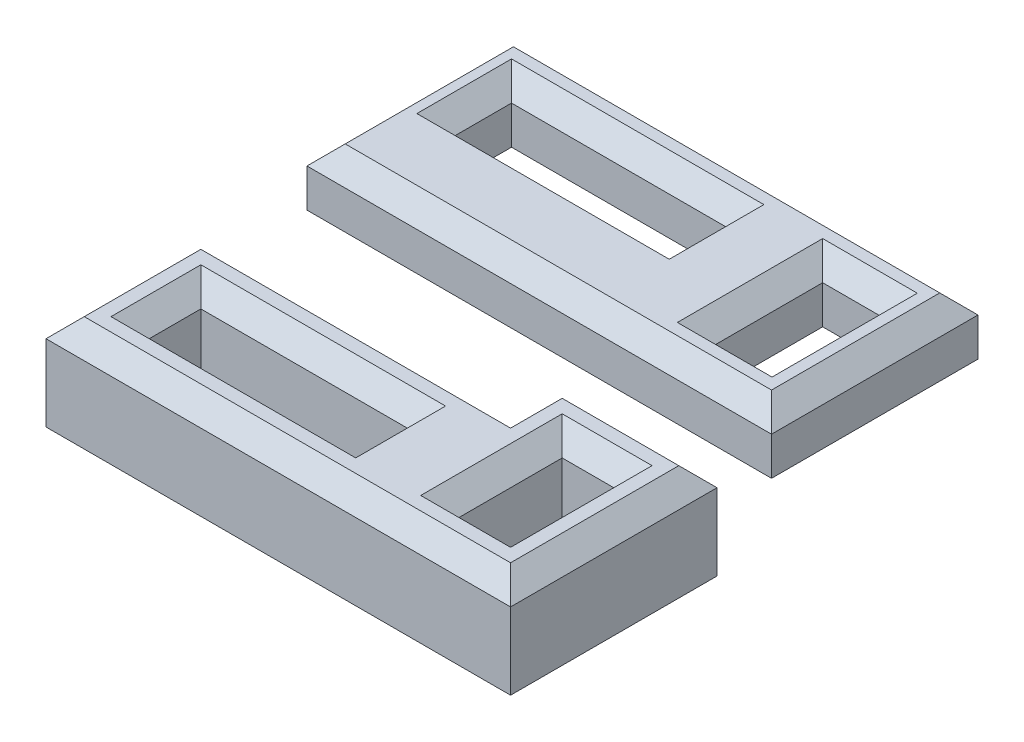
SolidWorks part; units mm, degrees
ref_plane "Front Plane" through (0, 0, 0) normal (0, 0, 1) x (1, 0, 0)
ref_plane "Top Plane" through (0, 0, 0) normal (0, 1, 0) x (1, 0, 0)
ref_plane "Right Plane" through (0, 0, 0) normal (1, 0, 0) x (0, 0, -1)
sketch "Sketch1" plane through (0, 0, 0) normal (0, 1, 0) x (1, 0, 0)
  line L12 (-12.15, -5.4) -> (12.15, -5.4)
  line L23 (4.05, 2.7) -> (6.75, 2.7) construction
  line L24 (-9.45, 0) -> (-9.45, 2.7) construction
  line L25 (12.15, 2.7) -> (9.45, 2.7) construction
  line L26 (-12.15, -2.7) -> (-9.45, -2.7) construction
  line L27 (9.45, 2.7) -> (9.45, 5.4) construction
  line L28 (-9.45, -2.7) -> (-9.45, -5.4) construction
  line L29 (4.05, -2.7) -> (6.75, -2.7) construction
  line L30 (1.35, -2.7) -> (4.05, -2.7) construction
  line L31 (-9.45, -2.7) -> (9.45, 2.7) construction
  line L32 (4.05, 2.7) -> (4.05, 5.4)
  line L33 (-12.15, 2.7) -> (4.05, 2.7)
  line L34 (12.15, -5.4) -> (12.15, 5.4)
  line L35 (4.05, 5.4) -> (12.15, 5.4)
  line L36 (-12.15, -5.4) -> (-12.15, 2.7)
  line L37 (9.45, -2.7) -> (9.45, 2.7)
  line L38 (6.75, 2.7) -> (9.45, 2.7)
  line L39 (6.75, -2.7) -> (6.75, 2.7)
  line L40 (6.75, -2.7) -> (9.45, -2.7)
  line L41 (1.35, -2.7) -> (1.35, 0)
  line L42 (-9.45, 0) -> (1.35, 0)
  line L43 (-9.45, -2.7) -> (-9.45, 0)
  line L44 (-9.45, -2.7) -> (1.35, -2.7)
  point P0 (-4.7205, 3.7182)
  dimension "D1" = 8.1
  dimension "D2" = 24.3
  dimension "D3" = 2.7
extrude "Boss-Extrude1" add sketch "Sketch1" along normal blind 2 and the other way blind 2
sketch "Sketch2" plane through (0, -2, 0) normal (0, -1, 0) x (1, 0, 0)
  line L0 (6.75, 2.7) -> (9.45, 2.7) construction
  line L1 (9.45, -2.7) -> (6.75, -2.7) construction
  line L4 (1.35, 2.7) -> (1.35, 0) construction
  line L5 (-9.45, 0) -> (-9.45, 2.7) construction
  line L6 (0.5, 1.35) -> (1.35, 1.35) construction
  line L7 (-8.6, 1.85) -> (-7.6, 1.85)
  line L8 (-8.6, 1.85) -> (-8.6, 0.85)
  line L9 (-8.6, 0.85) -> (-7.6, 0.85)
  line L10 (-7.6, 1.85) -> (-7.6, 0.85)
  line L11 (-5.9, 1.85) -> (-4.9, 1.85)
  line L12 (-5.9, 1.85) -> (-5.9, 0.85)
  line L13 (-5.9, 0.85) -> (-4.9, 0.85)
  line L14 (-4.9, 1.85) -> (-4.9, 0.85)
  line L15 (-3.2, 1.85) -> (-2.2, 1.85)
  line L16 (-3.2, 1.85) -> (-3.2, 0.85)
  line L17 (-3.2, 0.85) -> (-2.2, 0.85)
  line L18 (-2.2, 1.85) -> (-2.2, 0.85)
  line L19 (-0.5, 1.85) -> (0.5, 1.85)
  line L20 (-0.5, 1.85) -> (-0.5, 0.85)
  line L21 (-0.5, 0.85) -> (0.5, 0.85)
  line L22 (0.5, 1.85) -> (0.5, 0.85)
  line L23 (7.6, 1.85) -> (8.6, 1.85)
  line L24 (7.6, 1.85) -> (7.6, 0.85)
  line L25 (7.6, 0.85) -> (8.6, 0.85)
  line L26 (8.6, 1.85) -> (8.6, 0.85)
  line L27 (7.6, -0.85) -> (8.6, -0.85)
  line L28 (7.6, -0.85) -> (7.6, -1.85)
  line L29 (7.6, -1.85) -> (8.6, -1.85)
  line L30 (8.6, -0.85) -> (8.6, -1.85)
  line L31 (8.1, -2.7) -> (8.1, -1.85) construction
  line L32 (-12.15, 5.4) -> (12.15, 5.4)
  line L33 (12.15, 5.4) -> (12.15, -5.4)
  line L34 (-7.6, 1.35) -> (-6.75, 1.35) construction
  line L35 (-6.75, 1.35) -> (-5.9, 1.35) construction
  line L36 (8.1, -0.85) -> (8.1, 0) construction
  line L37 (-4.9, 1.35) -> (-4.05, 1.35) construction
  line L38 (-4.05, 1.35) -> (-3.2, 1.35) construction
  line L39 (8.1, 1.85) -> (8.1, 2.7) construction
  line L40 (-8.6, 1.35) -> (-9.45, 1.35) construction
  line L41 (12.15, -5.4) -> (4.05, -5.4)
  line L42 (4.05, -5.4) -> (4.05, -2.7) construction
  line L43 (8.1, 0) -> (8.1, 0.85) construction
  line L44 (12.15, -5.4) -> (4.05, -5.4) construction
  line L45 (-2.2, 1.35) -> (-1.35, 1.35) construction
  line L46 (-1.35, 1.35) -> (-0.5, 1.35) construction
  line L47 (4.05, -5.4) -> (4.05, -2.7)
  line L48 (4.05, -2.7) -> (-12.15, -2.7)
  line L49 (-12.15, -2.7) -> (-12.15, 5.4)
  point P6 (1.35, 1.35)
  dimension "D1" = 1
extrude "Boss-Extrude2" add sketch "Sketch2" along normal blind 1
chamfer "Chamfer3" distance 1 angle 45 14 edges at (0, 2, 5.4) (-4.05, 2, 2.7) (1.35, 2, 1.35) (-4.05, 2, 0) (-9.45, 2, 1.35) (-4.05, 2, -2.7) (4.05, 2, -4.05) (8.1, 2, -5.4) (12.15, 2, 0) (-12.15, 2, 1.35) (8.1, 2, 2.7) (9.45, 2, 0) (8.1, 2, -2.7) (6.75, 2, 0)
sketch "Sketch3" plane through (0, 0, 0) normal (0, 1, 0) x (1, 0, 0)
  line L1 (-9.65, 16.45) -> (1.55, 16.45)
  line L2 (-9.65, 16.45) -> (-9.65, 13.5)
  line L3 (-9.65, 13.5) -> (1.55, 13.5)
  line L4 (1.55, 16.45) -> (1.55, 13.5)
  line L5 (-4.05, -2.7) -> (-4.05, 13.5) construction
  line L6 (-9.45, -2.7) -> (1.35, -2.7) construction
  line L7 (4.05, 5.4) -> (12.15, 5.4) construction
  line L8 (12.15, 5.4) -> (12.15, -5.4) construction
  line L9 (6.625, 16.45) -> (9.575, 16.45)
  line L10 (6.625, 16.45) -> (6.625, 10.85)
  line L11 (6.625, 10.85) -> (9.575, 10.85)
  line L12 (9.575, 16.45) -> (9.575, 10.85)
  line L13 (-12.15, 19.05) -> (12.15, 19.05)
  line L14 (-12.15, 19.05) -> (-12.15, 8.25)
  line L15 (-12.15, 8.25) -> (12.15, 8.25)
  line L16 (12.15, 19.05) -> (12.15, 8.25)
  line L17 (12.15, -5.4) -> (-12.15, -5.4) construction
  line L18 (9.575, 13.65) -> (12.15, 13.65) construction
  line L19 (4.05, 5.4) -> (12.15, 5.4)
  line L20 (8.1, 2.7) -> (8.1, 10.85) construction
  line L21 (9.45, 2.7) -> (6.75, 2.7) construction
  point P5 (-4.05, 5.4)
  dimension "D1" = 2.95
  dimension "D2" = 11.2
  dimension "D3" = 5.6
  dimension "D4" = 5.075
extrude "Boss-Extrude3" add sketch "Sketch3" along normal blind 3 separate body contours L16 L13 L14 L15 L1 L4 L3 L2 L9 L12 L11 L10 region at (0, 0, -13.4444)
chamfer "Chamfer4" distance 1 angle 45 12 edges at (6.625, 3, -13.65) (8.1, 3, -10.85) (9.575, 3, -13.65) (8.1, 3, -16.45) (-9.65, 3, -14.975) (-4.05, 3, -13.5) (1.55, 3, -14.975) (-4.05, 3, -16.45) (0, 3, -8.25) (-12.15, 3, -13.65) (0, 3, -19.05) (12.15, 3, -13.65)
